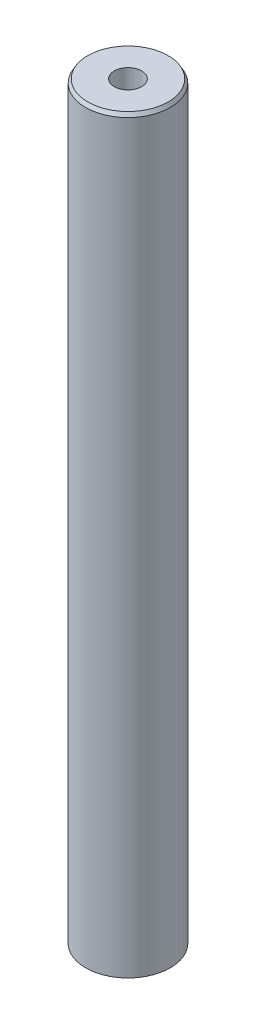
SolidWorks part; units mm, degrees
ref_plane "Front Plane" through (0, 0, 0) normal (0, 0, 1) x (1, 0, 0)
ref_plane "Top Plane" through (0, 0, 0) normal (0, 1, 0) x (1, 0, 0)
ref_plane "Right Plane" through (0, 0, 0) normal (1, 0, 0) x (0, 0, -1)
sketch "Sketch1" plane through (0, 0, 0) normal (0, 1, 0) x (1, 0, 0)
  circle A0 centre (0, 0) radius 15
  dimension "SHAFT_OD" = 30
extrude "Boss-Extrude1" add sketch "Sketch1" along normal blind 266.2579
sketch "Sketch2" plane through (0, 0, 0) normal (0, 1, 0) x (1, 0, 0)
  circle A0 centre (0, 0) radius 4.8518
  dimension "BORE_D" = 9.7036
extrude "Cut-Extrude1" cut sketch "Sketch2" along normal through all
chamfer "Chamfer1" distance 1.3193 angle 30 2 edges at (0, 266.2579, 15) (0, 0, 15) first distance on face at (0, 266.2579, 15) first distance on face at (0, 0, 4.8518)
